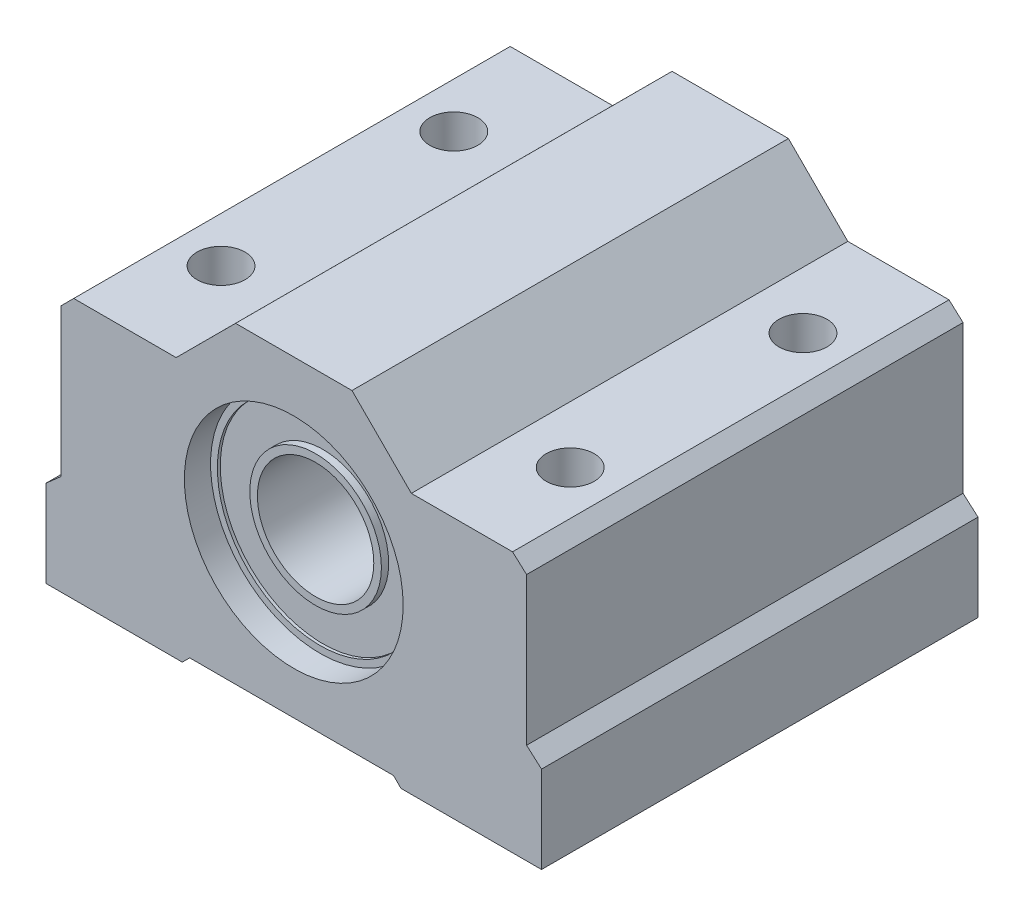
SolidWorks part; units mm, degrees
ref_plane "Plan de face" through (0, 0, 0) normal (0, 0, 1) x (1, 0, 0)
ref_plane "Plan de dessus" through (0, 0, 0) normal (0, 1, 0) x (1, 0, 0)
ref_plane "Plan de droite" through (0, 0, 0) normal (1, 0, 0) x (0, 0, -1)
sketch "Esquisse1" plane through (0, 0, 0) normal (0, 0, 1) x (1, 0, 0)
  line L0 (37.9997, 220.8672) -> (334.6664, 220.8672) construction
  line L1 (-17.03, -10.9738) -> (-7.6627, -10.9738)
  line L2 (-7.6627, -10.9738) -> (-7.1532, -10.4644)
  line L3 (-7.1532, -10.4644) -> (6.8576, -10.4644)
  line L4 (6.8576, -10.4644) -> (7.3671, -10.9738)
  line L5 (7.3671, -10.9738) -> (17.03, -10.9738)
  line L6 (17.03, -10.9738) -> (17.03, -4.9953)
  line L7 (17.03, -4.9953) -> (16.0028, -4.0892)
  line L8 (16.0028, -4.0892) -> (16.0028, 6.0714)
  line L9 (16.0028, 6.0714) -> (15.0375, 6.9443)
  line L10 (15.0375, 6.9443) -> (8.0819, 6.9443)
  line L11 (8.0819, 6.9443) -> (4, 11.0262)
  line L12 (4, 11.0262) -> (-4, 11.0262)
  line L13 (-4, 11.0262) -> (-8.0839, 6.9443)
  line L14 (-8.0839, 6.9443) -> (-15.1244, 6.9443)
  line L15 (-15.1244, 6.9443) -> (-15.9972, 6.0714)
  line L16 (-15.9972, 6.0714) -> (-15.9972, -4.0892)
  line L17 (-15.9972, -4.0892) -> (-17.03, -5.0045)
  line L18 (-17.03, -5.0045) -> (-17.03, -10.9738)
  circle A0 centre (0, 0) radius 4
  circle A1 centre (0, 0) radius 4.5234
  circle A2 centre (0, 0) radius 7.0518
  circle A3 centre (0, 0) radius 7.519
  dimension "D1" = 8
  dimension "D2" = 22
  dimension "D3" = 34.06
  dimension "D4" = 17.03
  dimension "D5" = 32
  dimension "D6" = 8
  dimension "D7" = 4
extrude "Boss.-Extru.1" add sketch "Esquisse1" against normal blind 30 contours L17 L18 L1 L2 L3 L4 L5 L6 L7 L8 L9 L10 L11 L12 L13 L14 L15 L16 A3 region at (-16.6245, -7.9891, 0)
extrude "Boss.-Extru.2" add sketch "Esquisse1<3>" against normal blind 28 separate body contours A2 A1 region at (-6.8523, 0, 0)
sketch "Esquisse1<3>" plane through (0, 0, 0) normal (0, 0, 1) x (1, 0, 0) same geometry as "Esquisse1"
extrude "Boss.-Extru.3" add sketch "Esquisse1<4>" against normal blind 30 contours A3 A2 region at (-7.3063, 0, 0)
sketch "Esquisse1<4>" plane through (0, 0, 0) normal (0, 0, 1) x (1, 0, 0) same geometry as "Esquisse1"
extrude "Boss.-Extru.4" add sketch "Esquisse1<5>" against normal blind 28.5 contours A1 A0 region at (-4.3955, 0, 0)
sketch "Esquisse1<5>" plane through (0, 0, 0) normal (0, 0, 1) x (1, 0, 0) same geometry as "Esquisse1"
extrude "Enlèv. mat.-Extru.1" cut sketch "Esquisse1<6>" against normal blind 1.5 contours A1 A0 region at (-4.3955, 0, 0)
sketch "Esquisse1<6>" plane through (0, 0, 0) normal (0, 0, 1) x (1, 0, 0) same geometry as "Esquisse1"
extrude "Enlèv. mat.-Extru.2" cut sketch "Esquisse1<7>" against normal blind 2 contours A2 A1 region at (-6.8523, 0, 0)
sketch "Esquisse1<7>" plane through (0, 0, 0) normal (0, 0, 1) x (1, 0, 0) same geometry as "Esquisse1"
extrude "Enlèv. mat.-Extru.3" cut sketch "Esquisse1<8>" against normal blind 1.8 contours A3 A2 region at (-7.3063, 0, 0)
sketch "Esquisse1<8>" plane through (0, 0, 0) normal (0, 0, 1) x (1, 0, 0) same geometry as "Esquisse1"
extrude "Enlèv. mat.-Extru.4" cut sketch "Esquisse1<9>" along normal blind 1.8 from surface contours A3 A2 region at (-7.3063, 0, 0) starting at face at (-0.0372, -1.1683, -30)
sketch "Esquisse1<9>" plane through (0, 0, 0) normal (0, 0, 1) x (1, 0, 0) same geometry as "Esquisse1"
sketch "Esquisse2" plane through (0, -10.9738, 0) normal (0, -1, 0) x (1, 0, 0)
  line L0 (74.1667, 293.5) -> (370.8333, 293.5) construction
  line L1 (7.3671, 0) -> (17.03, 0) construction
  line L2 (-17.03, -30) -> (-17.03, 0) construction
  circle A0 centre (-12, -7) radius 1.65
  circle A1 centre (12, -7) radius 1.65
  circle A2 centre (12, -23) radius 1.65
  circle A3 centre (-12, -23) radius 1.65
  dimension "D1" = 3.3
  dimension "D2" = 3.3
  dimension "D3" = 3.3
  dimension "D4" = 3.3
  dimension "D10" = 16
  dimension "D5" = 0
  dimension "D6" = 0
  dimension "D7" = 0
  dimension "D8" = 0
  dimension "D9" = 24
  dimension "D11" = 7
  dimension "D12" = 5.03
extrude "Enlèv. mat.-Extru.5" cut sketch "Esquisse2" against normal blind 21.8
